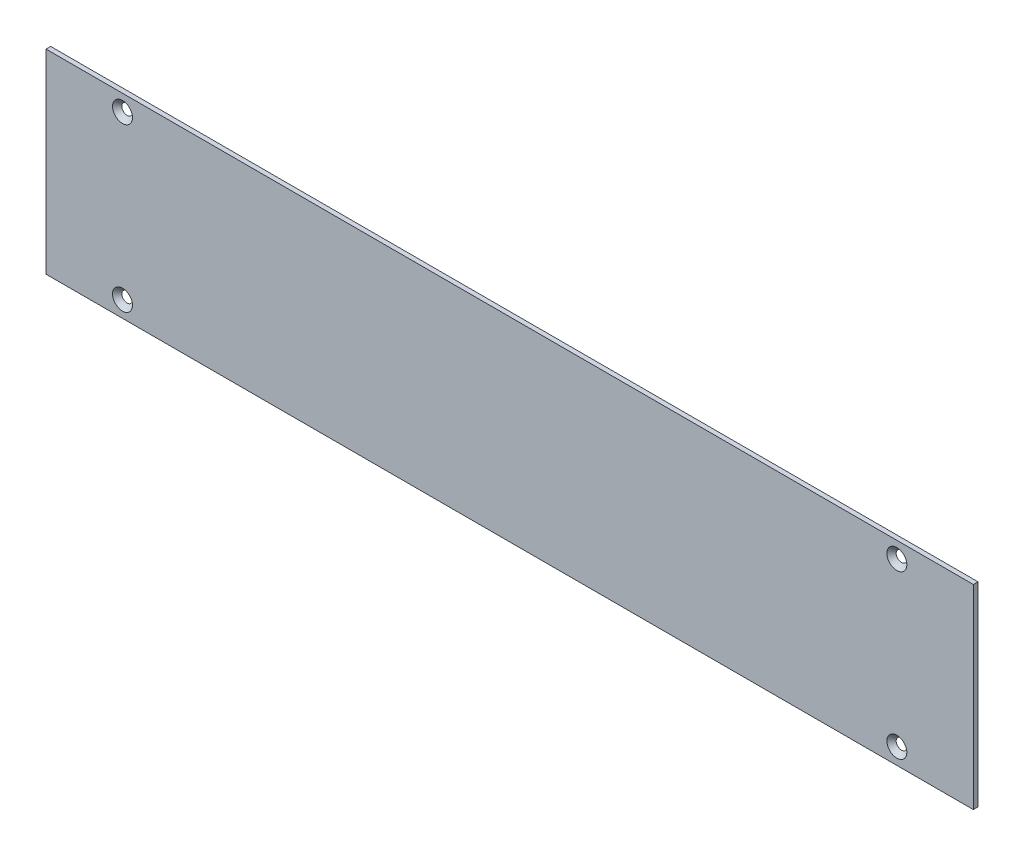
SolidWorks part; units mm, degrees
material "1060 Сплав"
ref_plane "Front" through (0, 0, 0) normal (0, 0, 1) x (1, 0, 0)
ref_plane "Top" through (0, 0, 0) normal (0, 1, 0) x (1, 0, 0)
ref_plane "Right" through (0, 0, 0) normal (1, 0, 0) x (0, 0, -1)
sketch "Эскиз1" plane through (0, 0, 0) normal (0, 0, 1) x (1, 0, 0)
  line L1 (0, 0) -> (400, 0)
  line L2 (0, 0) -> (0, 84.1)
  line L3 (0, 84.1) -> (400, 84.1)
  line L4 (400, 0) -> (400, 84.1)
  dimension "D1" = 400
  dimension "D2" = 84.1
extrude "Бобышка-Вытянуть1" add sketch "Эскиз1" along normal blind 2
sketch "Эскиз2" plane through (0, 0, 2) normal (0, 0, 1) x (1, 0, 0)
  line L0 (0, 84.1) -> (0, 0) construction
  line L1 (400, 84.1) -> (0, 84.1) construction
  line L2 (400, 0) -> (400, 84.1) construction
  line L3 (0, 0) -> (400, 0) construction
  circle A0 centre (33, 77.1) radius 2.25
  circle A1 centre (367, 77.1) radius 2.25
  circle A2 centre (367, 7) radius 2.25
  circle A3 centre (33, 7) radius 2.25
  dimension "D1" = 4.5
  dimension "D2" = 33
  dimension "D3" = 7
  dimension "D6" = 33
  dimension "D7" = 7
  dimension "D4" = 2
  dimension "D5" = 2
extrude "Вырез-Вытянуть1" cut sketch "Эскиз2" against normal through all
chamfer "Фаска1" distance 2.05 angle 45 4 edges at (369.25, 7, 2) (369.25, 77.1, 2) (35.25, 7, 2) (35.25, 77.1, 2)
